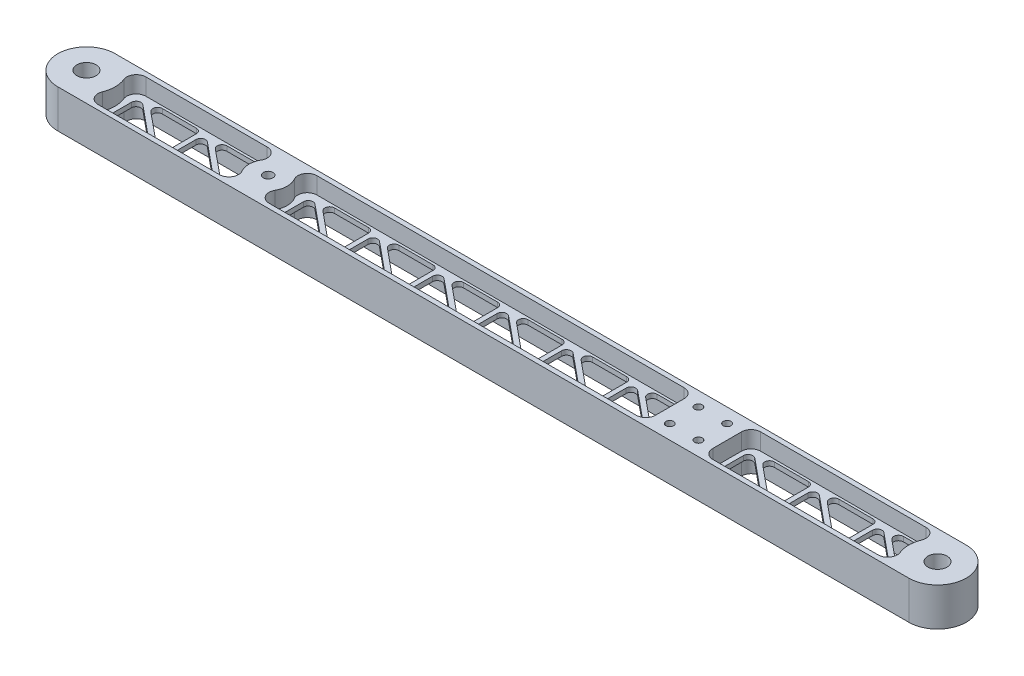
SolidWorks part; units mm, degrees
note: The reader was unsure of these and kept them because the rebuilt part matched: shared geometry of "Sketch13<4>".
material "7075-T6 (SN)"
ref_plane "Front Plane" through (0, 0, 0) normal (0, 0, 1) x (1, 0, 0)
ref_plane "Top Plane" through (0, 0, 0) normal (0, 1, 0) x (1, 0, 0)
ref_plane "Right Plane" through (0, 0, 0) normal (1, 0, 0) x (0, 0, -1)
sketch "Sketch2" plane through (0, 0, 0) normal (0, 1, 0) x (1, 0, 0)
  line L0 (0, 0) -> (120.65, 0)
  line L1 (0, 0) -> (565.15, 0)
  line L2 (0, 0) -> (0, 38.1) construction
  line L3 (0, 38.1) -> (565.15, 38.1)
  line L4 (565.15, 0) -> (565.15, 38.1) construction
  line L5 (120.65, 0) -> (120.65, 38.1) construction
  circle A0 centre (120.65, 19.05) radius 19.05
  arc A1 (565.15, 38.1) -> (565.15, 0) centre (565.15, 19.05) cw
  circle A2 centre (120.65, 19.05) radius 3.175
  circle A3 centre (565.15, 19.05) radius 6.35
  arc A4 (0, 38.1) -> (0, 0) centre (0, 19.05) ccw
  circle A5 centre (0, 19.05) radius 6.35
  dimension "D4" = 6.35
  dimension "D5" = 12.7
  dimension "D6" = 12.7
  dimension "D1" = 565.15
  dimension "D2" = 38.1
  dimension "D3" = 120.65
extrude "Boss-Extrude1" add sketch "Sketch2" along normal blind 25.4 contours A0 L3 L2 L0 | A0 A2 | A1 L3 A0 L1 A3
sketch "Sketch12" plane through (0, 0, -38.1) normal (0, 0, -1) x (-1, 0, 0)
  line L0 (-565.15, 25.4) -> (-425.45, 25.4)
  line L1 (0, 25.4) -> (-565.15, 25.4) construction
  line L2 (-387.35, 0) -> (-425.45, 0)
  line L3 (-425.45, 25.4) -> (-425.45, 0)
  line L5 (-387.35, 0) -> (-387.35, 25.4)
  line L6 (-425.45, 25.4) -> (-387.35, 25.4)
  line L7 (0, 0) -> (-565.15, 0) construction
  dimension "D1" = 139.7
  dimension "D2" = 38.1
sketch "Sketch13" plane through (0, 25.4, 0) normal (0, 1, 0) x (1, 0, 0)
  line L0 (565.15, 38.1) -> (565.15, 0) construction
  line L1 (0, 38.1) -> (0, 0) construction
  line L2 (565.15, 38.1) -> (565.15, 0) construction
  line L3 (565.15, 34.925) -> (0, 34.925)
  line L4 (0, 3.175) -> (565.15, 3.175)
  line L5 (565.15, 38.1) -> (425.45, 38.1) construction
  line L6 (0, 0) -> (565.15, 0) construction
  line L7 (19.05, 19.05) -> (22.225, 19.05) construction
  line L8 (22.225, 33.3375) -> (22.225, 4.7625)
  line L9 (22.225, 4.7625) -> (56.9185, 4.7625)
  line L10 (56.9185, 4.7625) -> (22.225, 33.3375)
  line L11 (27.219, 33.3375) -> (61.9125, 4.7625)
  line L12 (61.9125, 4.7625) -> (61.9125, 33.3375)
  line L13 (61.9125, 33.3375) -> (27.219, 33.3375)
  line L14 (65.0875, 33.3375) -> (65.0875, 4.7625)
  line L15 (65.0875, 4.7625) -> (99.781, 4.7625)
  line L16 (99.781, 4.7625) -> (65.0875, 33.3375)
  line L17 (70.0815, 33.3375) -> (104.775, 4.7625)
  line L18 (104.775, 4.7625) -> (104.775, 33.3375)
  line L19 (104.775, 33.3375) -> (70.0815, 33.3375)
  line L20 (61.9125, 19.05) -> (65.0875, 19.05) construction
  line L21 (350.8375, 33.3375) -> (350.8375, 4.7625)
  line L22 (350.8375, 4.7625) -> (384.175, 4.7625)
  line L23 (44.5658, 33.3375) -> (44.5658, 34.925) construction
  line L24 (39.5717, 4.7625) -> (39.5717, 3.175) construction
  line L25 (120.65, 34.925) -> (120.65, 3.175) construction
  line L26 (384.175, 5.8793) -> (350.8375, 33.3375)
  line L27 (355.8315, 33.3375) -> (384.175, 9.9926)
  line L28 (107.95, 19.05) -> (104.775, 19.05) construction
  line L29 (133.35, 19.05) -> (136.525, 19.05) construction
  line L30 (136.525, 33.3375) -> (136.525, 4.7625)
  line L31 (136.525, 4.7625) -> (171.2185, 4.7625)
  line L32 (171.2185, 4.7625) -> (136.525, 33.3375)
  line L33 (141.519, 33.3375) -> (176.2125, 4.7625)
  line L34 (176.2125, 4.7625) -> (176.2125, 33.3375)
  line L35 (176.2125, 33.3375) -> (141.519, 33.3375)
  line L36 (387.35, 38.1) -> (387.35, 0)
  line L37 (425.45, 38.1) -> (387.35, 38.1) construction
  line L38 (387.35, 0) -> (425.45, 0)
  line L39 (425.45, 0) -> (425.45, 38.1)
  line L40 (387.35, 38.1) -> (425.45, 38.1) construction
  line L41 (425.45, 38.1) -> (387.35, 38.1)
  line L42 (179.3875, 33.3375) -> (179.3875, 4.7625)
  line L43 (179.3875, 4.7625) -> (214.081, 4.7625)
  line L44 (214.081, 4.7625) -> (179.3875, 33.3375)
  line L45 (184.3815, 33.3375) -> (219.075, 4.7625)
  line L46 (219.075, 4.7625) -> (219.075, 33.3375)
  line L47 (219.075, 33.3375) -> (184.3815, 33.3375)
  line L48 (176.2125, 19.05) -> (179.3875, 19.05) construction
  line L49 (222.25, 33.3375) -> (222.25, 4.7625)
  line L50 (222.25, 4.7625) -> (256.9435, 4.7625)
  line L51 (256.9435, 4.7625) -> (222.25, 33.3375)
  line L52 (227.244, 33.3375) -> (261.9375, 4.7625)
  line L53 (261.9375, 4.7625) -> (261.9375, 33.3375)
  line L54 (261.9375, 33.3375) -> (227.244, 33.3375)
  line L55 (219.075, 19.05) -> (222.25, 19.05) construction
  line L56 (265.1125, 33.3375) -> (265.1125, 4.7625)
  line L57 (265.1125, 4.7625) -> (299.806, 4.7625)
  line L58 (299.806, 4.7625) -> (265.1125, 33.3375)
  line L59 (270.1065, 33.3375) -> (304.8, 4.7625)
  line L60 (304.8, 4.7625) -> (304.8, 33.3375)
  line L61 (304.8, 33.3375) -> (270.1065, 33.3375)
  line L62 (261.9375, 19.05) -> (265.1125, 19.05) construction
  line L63 (307.975, 33.3375) -> (307.975, 4.7625)
  line L64 (307.975, 4.7625) -> (342.6685, 4.7625)
  line L65 (342.6685, 4.7625) -> (307.975, 33.3375)
  line L66 (312.969, 33.3375) -> (347.6625, 4.7625)
  line L67 (347.6625, 4.7625) -> (347.6625, 33.3375)
  line L68 (347.6625, 33.3375) -> (312.969, 33.3375)
  line L69 (304.8, 19.05) -> (307.975, 19.05) construction
  line L70 (548.126, 33.3375) -> (519.344, 33.3375)
  line L71 (530.4996, 20.036) -> (532.5181, 22.4868) construction
  line L72 (546.6492, 6.7345) -> (514.35, 33.3375)
  line L73 (384.175, 5.8793) -> (384.175, 4.7625)
  line L75 (384.175, 5.8793) -> (350.8375, 33.3375)
  line L76 (384.175, 33.3375) -> (355.8315, 33.3375)
  line L77 (347.6625, 19.05) -> (350.8375, 19.05) construction
  line L78 (384.175, 33.3375) -> (384.175, 9.9926)
  line L84 (425.45, 19.05) -> (428.625, 19.05) construction
  line L85 (428.625, 33.3375) -> (428.625, 4.7625)
  line L86 (428.625, 4.7625) -> (463.3185, 4.7625)
  line L87 (463.3185, 4.7625) -> (428.625, 33.3375)
  line L88 (433.619, 33.3375) -> (468.3125, 4.7625)
  line L89 (468.3125, 4.7625) -> (468.3125, 33.3375)
  line L90 (468.3125, 33.3375) -> (433.619, 33.3375)
  line L91 (471.4875, 33.3375) -> (471.4875, 4.7625)
  line L92 (471.4875, 4.7625) -> (506.181, 4.7625)
  line L93 (506.181, 4.7625) -> (471.4875, 33.3375)
  line L94 (476.4815, 33.3375) -> (511.175, 4.7625)
  line L95 (511.175, 4.7625) -> (511.175, 33.3375)
  line L96 (511.175, 33.3375) -> (476.4815, 33.3375)
  line L97 (468.3125, 19.05) -> (471.4875, 19.05) construction
  line L98 (514.35, 33.3375) -> (514.35, 4.7625)
  line L99 (514.35, 4.7625) -> (548.126, 4.7625)
  line L101 (519.344, 33.3375) -> (543.6845, 13.2897)
  line L104 (511.175, 19.05) -> (514.35, 19.05) construction
  line L112 (387.35, 19.05) -> (425.45, 19.05) construction
  line L113 (565.15, 19.05) -> (546.1, 19.05) construction
  line L114 (546.1, 19.05) -> (546.1, 38.1) construction
  line L115 (546.1, 38.1) -> (546.1, 3.175) construction
  line L116 (406.4, 38.1) -> (406.4, 0) construction
  line L117 (396.875, 38.1) -> (396.875, 0) construction
  line L118 (415.925, 0) -> (415.925, 38.1) construction
  line L119 (387.35, 29.6333) -> (425.45, 29.6333) construction
  line L120 (387.35, 8.4667) -> (425.45, 8.4667) construction
  line L121 (568.4516, 33.3375) -> (565.15, 33.3375) [skipped]
  line L122 (554.0375, 4.7625) -> (554.0375, 33.3375) [skipped]
  line L123 (554.8268, -0.0009) -> (549.9493, 4.0164) [skipped]
  line L124 (390.525, 29.6333) -> (390.525, 33.3375) [skipped]
  circle A0 centre (565.15, 19.05) radius 19.05
  arc A1 (109.6515, 25.4) -> (109.6515, 12.7) centre (120.65, 19.05) ccw
  circle A2 centre (0, 19.05) radius 19.05
  arc A3 (104.1522, 34.925) -> (109.6515, 25.4) centre (104.1522, 28.575) cw
  arc A4 (546.6492, 6.7345) -> (548.126, 4.7625) centre (565.15, 19.05) ccw
  arc A5 (548.126, 33.3375) -> (543.6845, 13.2897) centre (565.15, 19.05) ccw
  arc A6 (109.6515, 12.7) -> (104.1522, 3.175) centre (104.1522, 9.525) cw
  arc A7 (131.6485, 12.7) -> (137.1478, 3.175) centre (137.1478, 9.525) ccw
  arc A8 (137.1478, 34.925) -> (131.6485, 25.4) centre (137.1478, 28.575) ccw
  arc A9 (131.6485, 12.7) -> (131.6485, 25.4) centre (120.65, 19.05) ccw
  point P164 (406.4, 29.6333)
  dimension "D1" = 25.4
  dimension "D9" = 3.175
  dimension "D30" = 8.4667
  dimension "D31" = 3.175
  dimension "D19" = 3.175
  dimension "D25" = 3.175
  dimension "D4" = 6.35
  dimension "D2" = 3.175
  dimension "D3" = 3.175
  dimension "Triangle Size" = 1.5875
  dimension "D6" = 3.175
  dimension "D7" = 3.175
  dimension "D10" = 3.175
  dimension "D11" = 3.175
  dimension "D14" = 3.175
  dimension "D15" = 139.7
  dimension "D16" = 38.1
  dimension "D17" = 6
  dimension "D18" = 3.175
  dimension "D20" = 3.175
  dimension "D23" = 3.175
  dimension "D26" = 3.175
  dimension "D27" = 9.525
  dimension "D28" = 9.525
  dimension "D29" = 8.4667
  dimension "D8" = 2
  dimension "D24" = 3
extrude "Cut-Extrude2" cut sketch "Sketch13" against normal up to next
extrude "Cut-Extrude3" cut sketch "Sketch13<4>" against normal blind 11.1125
sketch "Sketch13<4>" plane through (0, 25.4, 0) normal (0, 1, 0) x (1, 0, 0) same geometry as "Sketch13"
ref_plane "Plane1" through (0, 12.7, 0) normal (0, -1, 0) x (-1, 0, 0)
mirror "Mirror1" about plane through (0, 12.7, 0) normal (0, -1, 0) of "Cut-Extrude3"
fillet "Fillet1" radius 3.175 63 edges at (104.775, 12.7, -33.3375) (104.775, 12.7, -4.7625) (70.0815, 12.7, -33.3375) (99.781, 12.7, -4.7625) (65.0875, 12.7, -4.7625) (65.0875, 12.7, -33.3375) (61.9125, 12.7, -33.3375) (61.9125, 12.7, -4.7625) (27.219, 12.7, -33.3375) (56.9185, 12.7, -4.7625) (22.225, 12.7, -4.7625) (22.225, 12.7, -33.3375) (347.6625, 12.7, -33.3375) (347.6625, 12.7, -4.7625) (312.969, 12.7, -33.3375) (342.6685, 12.7, -4.7625) (307.975, 12.7, -4.7625) (307.975, 12.7, -33.3375) (304.8, 12.7, -33.3375) (304.8, 12.7, -4.7625) (270.1065, 12.7, -33.3375) (299.806, 12.7, -4.7625) (265.1125, 12.7, -4.7625) (265.1125, 12.7, -33.3375) (261.9375, 12.7, -33.3375) (261.9375, 12.7, -4.7625) (227.244, 12.7, -33.3375) (256.9435, 12.7, -4.7625) (222.25, 12.7, -4.7625) (222.25, 12.7, -33.3375) (219.075, 12.7, -33.3375) (219.075, 12.7, -4.7625) (184.3815, 12.7, -33.3375) (214.081, 12.7, -4.7625) (179.3875, 12.7, -4.7625) (179.3875, 12.7, -33.3375) (176.2125, 12.7, -33.3375) (176.2125, 12.7, -4.7625) (141.519, 12.7, -33.3375) (171.2185, 12.7, -4.7625) (136.525, 12.7, -4.7625) (136.525, 12.7, -33.3375) (514.35, 12.7, -4.7625) (511.175, 12.7, -33.3375) (511.175, 12.7, -4.7625) (476.4815, 12.7, -33.3375) (506.181, 12.7, -4.7625) (471.4875, 12.7, -4.7625) (471.4875, 12.7, -33.3375) (468.3125, 12.7, -33.3375) (468.3125, 12.7, -4.7625) (433.619, 12.7, -33.3375) (463.3185, 12.7, -4.7625) (428.625, 12.7, -4.7625) (428.625, 12.7, -33.3375) (548.126, 12.7, -33.3375) (543.6845, 12.7, -13.2897) (514.35, 12.7, -33.3375) (384.175, 12.7, -9.9926) (355.8315, 12.7, -33.3375) (384.175, 12.7, -33.3375) (350.8375, 12.7, -4.7625) (350.8375, 12.7, -33.3375)
hole_wizard "1/4-20 Tapped Hole1" positions "3DSketch1" profile "Sketch14" tap size "1/4-20" standard "ANSI Inch"
sketch3d "3DSketch1"
  line L5 (0, 25.4, -38.1) -> (565.15, 25.4, -38.1) construction
  line L8 (425.45, 25.4, -3.175) -> (425.45, 25.4, -34.925) construction
  line L9 (387.35, 25.4, -34.925) -> (387.35, 25.4, -3.175) construction
  line L10 (0, 25.4, 0) -> (565.15, 25.4, 0) construction
  point P17 (415.925, 25.4, -28.575)
  point P32 (396.875, 25.4, -28.575)
  point P34 (396.875, 25.4, -9.525)
  point P36 (415.925, 25.4, -9.525)
  dimension "D1" = 9.525
  dimension "D5" = 9.525
  dimension "D2" = 9.525
  dimension "D3" = 9.525
  dimension "D4" = 9.525
  dimension "D6" = 9.525
  dimension "D7" = 9.525
  dimension "D8" = 9.525
sketch "Sketch14" plane through (415.925, 25.4, -28.575) normal (1, 0, 0) x (0, 0, 1)
  line L0 (0, 0) -> (0, 20.5838)
  line L1 (0, 20.5838) -> (2.5527, 19.05)
  line L2 (2.5527, 19.05) -> (2.5527, 0)
  line L5 (2.5527, 0) -> (0, 0)
  line L10 (0, 20.5838) -> (-2.5527, 19.05) construction
  line L11 (0, -6.35) -> (0, 107.95) construction
  dimension "Tap Drill Dia." = 5.1054
  dimension "Tap Drill Depth" = 19.05
  dimension "Drill Angle" = 118
cosmetic thread "Hole Thread1" parameters "D1"=12.7, "D2"=6.35
cosmetic thread "Hole Thread2" parameters "D1"=12.7, "D2"=6.35
cosmetic thread "Hole Thread3" parameters "D1"=12.7, "D2"=6.35
cosmetic thread "Hole Thread4" parameters "D1"=12.7, "D2"=6.35
fillet "Fillet3" radius 3.175 4 edges at (547.3602, 14.2875, -5.728) (546.6492, 12.7, -6.7345) (548.126, 12.7, -4.7625) (547.3602, 11.1125, -5.728)
fillet "Fillet4" radius 3.175 1 edges at (519.344, 12.7, -33.3375)
fillet "Fillet5" radius 6.35 16 edges at (554.6197, 19.8438, -3.175) (554.6197, 19.8438, -34.925) (425.45, 19.8438, -3.175) (425.45, 19.8438, -34.925) (387.35, 19.8438, -3.175) (387.35, 19.8438, -34.925) (10.5303, 19.8438, -34.925) (10.5303, 19.8438, -3.175) (10.5303, 5.5562, -3.175) (10.5303, 5.5562, -34.925) (387.35, 5.5562, -34.925) (387.35, 5.5562, -3.175) (554.6197, 5.5562, -34.925) (554.6197, 5.5562, -3.175) (425.45, 5.5562, -3.175) (425.45, 5.5562, -34.925)
fillet "Fillet6" radius 3.175 4 edges at (384.175, 14.2875, -5.3209) (384.175, 12.7, -5.8793) (384.175, 12.7, -4.7625) (384.175, 11.1125, -5.3209)
